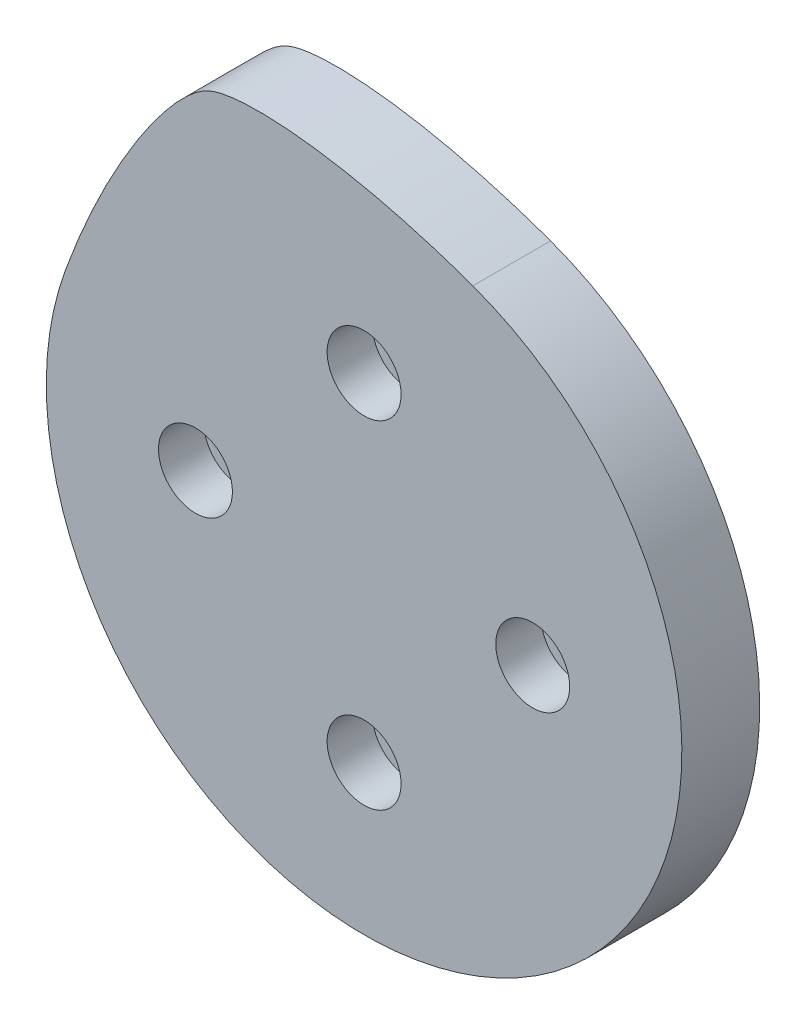
SolidWorks part; units mm, degrees
ref_plane "Front Plane" through (0, 0, 0) normal (1, 0, 0) x (0, 1, 0)
ref_plane "Top Plane" through (0, 0, 0) normal (0, 0, 1) x (0, 1, 0)
ref_plane "Right Plane" through (0, 0, 0) normal (0, 1, 0) x (-1, 0, 0)
sketch "Sketch1" plane through (0, 0, 0) normal (0, 0, 1) x (0, 1, 0)
  circle A0 centre (0, 0) radius 21
  circle A1 centre (0, 0) radius 13 construction
  circle A2 centre (0, 13) radius 1.6
  circle A3 centre (0, 13) radius 2.85
  circle A4 centre (13, 0) radius 2.85
  circle A5 centre (13, 0) radius 1.6
  circle A6 centre (0, -13) radius 2.85
  circle A7 centre (0, -13) radius 1.6
  circle A8 centre (-13, 0) radius 2.85
  circle A9 centre (-13, 0) radius 1.6
  point P19 (0, 0)
  dimension "D1" = 42
  dimension "D2" = 26
  dimension "D3" = 3.2
  dimension "D4" = 5.7
  dimension "D5" = 4
extrude "Boss-Extrude1" add sketch "Sketch1" along normal blind 6 contours A0 A8 A6 A4 A3 region at (0, 0, 0)
sketch "Sketch2" plane through (0, 0, 0) normal (0, 0, -1) x (1, 0, 0)
  line L0 (0, 0) -> (0, 28.5) construction
  line L1 (0, 0) -> (-12.0446, -25.8298) construction
  line L2 (0, 0) -> (-26.7812, -9.7476) construction
  line L3 (0, 0) -> (9.7476, -26.7812) construction
  line L4 (-13.7052, -25.0554) -> (-49.9575, -8.1507) construction
  line L5 (-8.9203, -47.1248) -> (-49.9627, 65.6383) construction
  line L6 (47.1248, -8.9203) -> (-65.6383, -49.9627) construction
  circle A0 centre (0, 0) radius 28.5 construction
  circle A1 centre (0, 0) radius 24.5
  spline S0 degree 3 poles (-23.0225, -8.3795) (-19.9443, -16.8367) (-14.7237, -24.6248) (-9.3995, -27.1075) (-0.0777, -26.1007) (8.3795, -23.0225) knots 0 0 0 0 0.45 0.55 1 1 1 1
  circle M5 centre (0, 0) radius 21
  dimension "D1" = 57
  dimension "D2" = 49
  dimension "D6" = 20
  dimension "D7" = 30
  dimension "D8" = 30
  dimension "D3" = 205
  dimension "D4" = 45
  dimension "D5" = 45
  dimension "D9" = 90
  dimension "D10" = 90
  dimension "D11" = 90
extrude "Boss-Extrude3" add sketch "Sketch2" against normal up to surface (6 mm away) contours A1 M5 | A1 S0 region at (19.5016, 13.6552, 0) region at (-10.6097, 22.7453, 0) up to face at (2.85, -13, 6)
extrude "Boss-Extrude2" add sketch "Sketch1<4>" along normal offset from surface (2.5 mm away) 3.5 contours A8 A9 | A3 A2 | A4 A5 | A6 A7 region at (-13, -2.7694, 0) region at (0, 10.2306, 0) region at (13, -2.7694, 0) region at (0, -15.7694, 0) up to face at (2.85, -13, 6)
sketch "Sketch1<4>" plane through (0, 0, 0) normal (0, 0, 1) x (0, 1, 0) same geometry as "Sketch1"
sketch "Sketch3" plane through (0, 0, 0) normal (0, 0, -1) x (1, 0, 0)
  circle A0 centre (0, 0) radius 21
  circle A1 centre (13, 0) radius 1.6
  circle A2 centre (0, 13) radius 1.6
  circle A3 centre (-13, 0) radius 1.6
  circle A4 centre (0, -13) radius 1.6
  dimension "D1" = 42
extrude "Boss-Extrude4" add sketch "Sketch3" along normal blind 0.5
